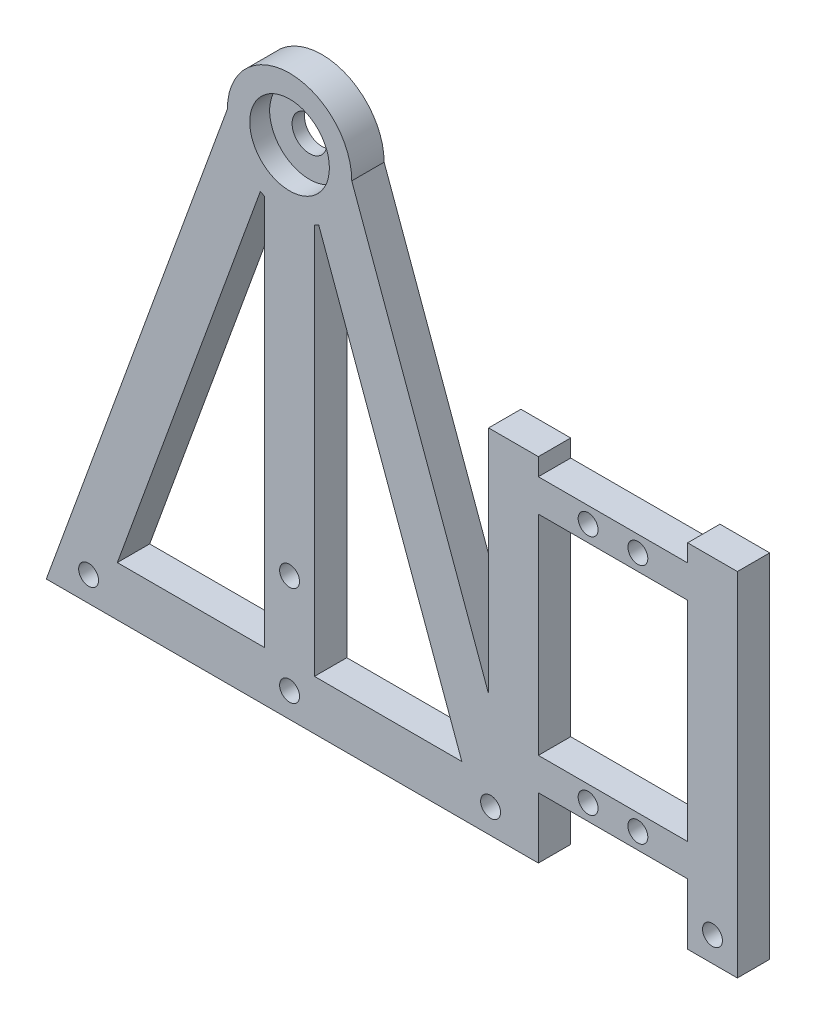
SolidWorks part; units mm, degrees
ref_plane "Front Plane" through (0, 0, 0) normal (0, 0, 1) x (1, 0, 0)
ref_plane "Top Plane" through (0, 0, 0) normal (0, 1, 0) x (1, 0, 0)
ref_plane "Right Plane" through (0, 0, 0) normal (1, 0, 0) x (0, 0, -1)
sketch "Sketch1" plane through (0, 0, 0) normal (0, 0, 1) x (1, 0, 0)
  line L0 (0, 0) -> (0, 100)
  line L1 (-48.897, 0) -> (48.897, 0)
  line L2 (-12.5, 100) -> (-48.897, 0)
  line L3 (12.5, 100) -> (48.897, 0)
  line L4 (0, 0) -> (0, 10)
  line L5 (-5.8742, 88.9662) -> (-34.6155, 10)
  line L6 (-34.6155, 10) -> (34.6155, 10)
  line L7 (5.8742, 88.9662) -> (34.6155, 10)
  line L8 (-3.1031, 96.5798) -> (-34.6155, 10) construction
  line L9 (3.1031, 96.5798) -> (34.6155, 10) construction
  line L10 (-5, 10) -> (5, 10)
  line L11 (-5, 10) -> (-5, 88.5436)
  line L12 (5, 10) -> (5, 88.5436)
  line L14 (-12.5, 100) -> (-48.897, 0) construction
  line L15 (0, 100) -> (0, 50) construction
  line L16 (0, 50) -> (65, 50) construction
  line L17 (65, 50) -> (65, 15.5) construction
  line L18 (60, 15.5) -> (70, 15.5) construction
  line L19 (65, 50) -> (65, 64) construction
  line L20 (60, 64) -> (70, 64) construction
  line L21 (65, 15.5) -> (65, 0) construction
  line L22 (65, 0) -> (80, 0) construction
  line L23 (48.897, 0) -> (80, 0)
  line L24 (80, 0) -> (90, 0)
  line L25 (80, 0) -> (80, 70.75)
  line L26 (50, 12.25) -> (80, 12.25)
  line L27 (50, 12.25) -> (50, 18.75)
  line L28 (50, 18.75) -> (80, 18.75)
  line L29 (80, 12.25) -> (80, 18.75)
  line L30 (50, 12.25) -> (80, 18.75) construction
  line L31 (50, 18.75) -> (80, 12.25) construction
  line L32 (50, 60.75) -> (80, 60.75)
  line L33 (50, 60.75) -> (50, 67.25)
  line L34 (50, 67.25) -> (80, 67.25)
  line L35 (80, 60.75) -> (80, 67.25)
  line L36 (50, 60.75) -> (80, 67.25) construction
  line L37 (50, 67.25) -> (80, 60.75) construction
  line L38 (80, 70.75) -> (90, 70.75)
  line L39 (90, 70.75) -> (90, 0)
  line L40 (80, 70.75) -> (40, 70.75)
  line L41 (80, 70.75) -> (80, 67.25)
  line L42 (40, 70.75) -> (40, 24.4444)
  line L43 (80, 12.25) -> (80, 0)
  line L44 (50, 67.25) -> (40, 67.25)
  line L45 (50, 60.75) -> (50, 18.75)
  line L46 (50, 12.25) -> (50, 0)
  line L47 (50, 0) -> (48.897, 0)
  line L48 (40, 24.4444) -> (48.897, 0)
  line L49 (50, 67.25) -> (80, 67.25)
  line L50 (50, 70.75) -> (80, 70.75)
  line L51 (40, 70.75) -> (50, 70.75)
  line L52 (40, 70.75) -> (40, 0)
  line L53 (40, 0) -> (50, 0)
  line L54 (50, 70.75) -> (50, 0)
  line L55 (80, 67.25) -> (80, 70.75)
  line L56 (50, 70.75) -> (50, 67.25)
  circle A2 centre (0, 100) radius 12.5
  arc A3 (12.5, 100) -> (5.8742, 88.9662) centre (0, 100) cw
  arc A4 (-5.8742, 88.9662) -> (-12.5, 100) centre (0, 100) cw
  arc A5 (-5, 88.5436) -> (5, 88.5436) centre (0, 100) ccw
  circle A6 centre (65, 50) radius 2.5 construction
  circle A7 centre (60, 64) radius 2.25 construction
  circle A8 centre (70, 64) radius 2.25 construction
  circle A9 centre (60, 15.5) radius 2.25 construction
  circle A10 centre (70, 15.5) radius 2.25 construction
  point P8 (0, 0)
  point P21 (0, 10)
  point P32 (65, 15.5)
  point P36 (65, 64)
  dimension "D2" = 25
  dimension "D9" = 5
  dimension "D16" = 4.5
  dimension "D17" = 4.5
  dimension "D18" = 4.5
  dimension "D19" = 4.5
  dimension "D1" = 100
  dimension "D3" = 70
  dimension "D4" = 10
  dimension "D6" = 10
  dimension "D7" = 50
  dimension "D8" = 65
  dimension "D10" = 10
  dimension "D11" = 34.5
  dimension "D12" = 14
  dimension "D13" = 10
  dimension "D14" = 15
  dimension "D15" = 10
  dimension "D20" = 6.5
  dimension "D21" = 6.5
  dimension "D22" = 0
  dimension "D23" = 0
  dimension "D24" = 10
  dimension "D25" = 3.5
  dimension "D5" = 10
extrude "Boss-Extrude1" add sketch "Sketch1" along normal blind 6.5 contours A2 | A4 L2 L1 L3 A3 L7 L6 L5 | L11 A5 L12 L10 | L52 L51 L54 L53 | L33 L32 L35 L34 | L25 L38 L39 L24 | L27 L26 L29 L28
sketch "Sketch2" plane through (0, 0, 6.5) normal (0, 0, 1) x (1, 0, 0)
  arc A0 (12.5, 100) -> (-12.5, 100) centre (0, 100) ccw construction
  arc A1 (12.5, 100) -> (-12.5, 100) centre (0, 100) ccw
  circle A2 centre (0, 100) radius 3.5
  circle A3 centre (0, 100) radius 8
  dimension "D1" = 7
  dimension "D2" = 16
extrude "Cut-Extrude1" cut sketch "Sketch2" against normal up to next contours A2
extrude "Cut-Extrude2" cut sketch "Sketch2<3>" against normal blind 4 contours A3 A2 region at (-7.7737, 100, 6.5)
sketch "Sketch2<3>" plane through (0, 0, 6.5) normal (0, 0, 1) x (1, 0, 0) same geometry as "Sketch2"
sketch "Sketch3" plane through (0, 0, 6.5) normal (0, 0, 1) x (1, 0, 0)
  line L0 (80, 5) -> (90, 5) construction
  line L1 (5.8742, 88.9662) -> (34.6155, 10) construction
  line L2 (5, 10) -> (34.6155, 10) construction
  line L3 (5, 10) -> (5, 88.5436) construction
  line L4 (-5, 10) -> (-5, 88.5436) construction
  line L5 (-5.8742, 88.9662) -> (-34.6155, 10) construction
  line L6 (-34.6155, 10) -> (-5, 10) construction
  line L7 (-12.5, 100) -> (-48.897, 0) construction
  line L8 (-48.897, 0) -> (50, 0) construction
  line L10 (5.8742, 88.9662) -> (34.6155, 10) construction
  line L11 (5, 10) -> (34.6155, 10) construction
  line L12 (5, 10) -> (5, 88.5436) construction
  line L13 (-5, 10) -> (-5, 88.5436) construction
  line L14 (-5.8742, 88.9662) -> (-34.6155, 10) construction
  line L15 (-34.6155, 10) -> (-5, 10) construction
  line L16 (-12.5, 100) -> (-48.897, 0) construction
  line L17 (-48.897, 0) -> (50, 0) construction
  line L18 (-48.897, 0) -> (-48.897, 5) construction
  line L20 (-48.897, 5) -> (48.897, 5) construction
  line L21 (-48.897, 5) -> (-40.397, 5) construction
  line L22 (48.897, 5) -> (40.397, 5) construction
  line L23 (0, 100) -> (0, 5) construction
  line L24 (0, 100) -> (0, 25) construction
  line L30 (80, 0) -> (80, 12.25) construction
  line L31 (90, 70.75) -> (90, 0) construction
  line L32 (85, 5) -> (85, 0) construction
  line L33 (80, 0) -> (90, 0) construction
  arc A0 (5, 88.5436) -> (5.8742, 88.9662) centre (0, 100) ccw construction
  arc A1 (-5.8742, 88.9662) -> (-5, 88.5436) centre (0, 100) ccw construction
  circle A2 centre (0, 100) radius 8 construction
  arc A3 (12.5, 100) -> (-12.5, 100) centre (0, 100) ccw construction
  arc A4 (5, 88.5436) -> (5.8742, 88.9662) centre (0, 100) ccw construction
  arc A5 (-5.8742, 88.9662) -> (-5, 88.5436) centre (0, 100) ccw construction
  circle A6 centre (0, 100) radius 8 construction
  arc A7 (12.5, 100) -> (-12.5, 100) centre (0, 100) ccw construction
  circle A8 centre (0, 5) radius 2
  circle A9 centre (40.397, 5) radius 2
  circle A10 centre (-40.397, 5) radius 2
  circle A11 centre (0, 25) radius 2
  circle A12 centre (-40.397, 5) radius 4
  circle A13 centre (0, 5) radius 4
  circle A14 centre (40.397, 5) radius 4
  circle A15 centre (0, 25) radius 4
  circle A16 centre (85, 5) radius 2
  circle A17 centre (85, 5) radius 4
  dimension "D6" = 4
  dimension "D7" = 4
  dimension "D8" = 4
  dimension "D9" = 4
  dimension "D10" = 8
  dimension "D11" = 8
  dimension "D12" = 8
  dimension "D13" = 8
  dimension "D15" = 4
  dimension "D16" = 8
  dimension "D1" = 5
  dimension "D2" = 5
  dimension "D3" = 8.5
  dimension "D4" = 8.5
  dimension "D5" = 75
  dimension "D14" = 5
extrude "Cut-Extrude4" cut sketch "Sketch3" against normal up to next contours A10 | A8 | A9 | A11 | A16 region at (0, 5, 6.5) region at (40.397, 5, 6.5) region at (-40.397, 5, 6.5)
sketch "Sketch5" plane through (0, 0, 6.5) normal (0, 0, 1) x (1, 0, 0)
  line L0 (50, 67.25) -> (80, 67.25) construction
  line L1 (65, 67.25) -> (65, 60.75) construction
  line L2 (50, 60.75) -> (80, 60.75) construction
  line L3 (60, 64) -> (70, 64) construction
  line L4 (50, 18.75) -> (80, 18.75) construction
  line L5 (65, 18.75) -> (65, 12.25) construction
  line L6 (50, 12.25) -> (80, 12.25) construction
  line L7 (60, 15.5) -> (70, 15.5) construction
  circle A0 centre (60, 64) radius 2
  circle A1 centre (70, 64) radius 2
  circle A2 centre (70, 15.5) radius 2
  circle A3 centre (60, 15.5) radius 2
  point P11 (65, 64)
  point P24 (65, 15.5)
  dimension "D2" = 4
  dimension "D3" = 4
  dimension "D5" = 4
  dimension "D6" = 4
  dimension "D1" = 10
  dimension "D4" = 10
extrude "Cut-Extrude6" cut sketch "Sketch5" against normal up to next
